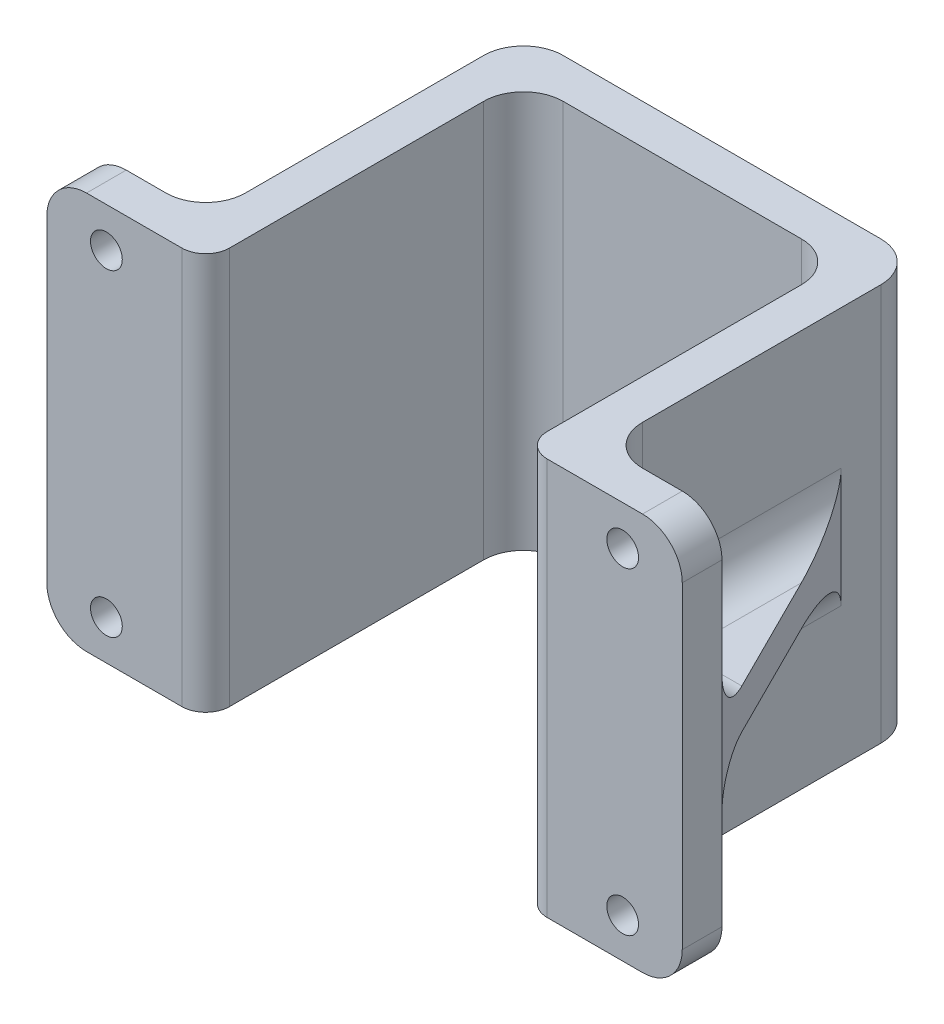
SolidWorks part; units mm, degrees
ref_plane "Front Plane" through (0, 0, 0) normal (0, 0, 1) x (1, 0, 0)
ref_plane "Top Plane" through (0, 0, 0) normal (0, 1, 0) x (1, 0, 0)
ref_plane "Right Plane" through (0, 0, 0) normal (1, 0, 0) x (0, 0, -1)
sketch "Sketch1" plane through (0, 0, 0) normal (0, 1, 0) x (1, 0, 0)
  line L0 (-40, 0) -> (-20, 0)
  line L1 (-20, 0) -> (-20, 40)
  line L2 (-20, 40) -> (20, 40)
  line L3 (20, 40) -> (20, 0)
  line L4 (20, 0) -> (40, 0)
  line L5 (40, 0) -> (40, 5)
  line L6 (40, 5) -> (25, 5)
  line L7 (25, 5) -> (25, 45)
  line L8 (25, 45) -> (-25, 45)
  line L9 (-25, 45) -> (-25, 5)
  line L10 (-25, 5) -> (-40, 5)
  line L11 (-40, 5) -> (-40, 0)
  line L12 (-20, 0) -> (20, 0) construction
  line L13 (0, 0) -> (0, 40) construction
  dimension "D1" = 40
  dimension "D2" = 40
  dimension "D3" = 5
  dimension "D4" = 5
  dimension "D5" = 5
  dimension "D6" = 5
  dimension "D7" = 15
  dimension "D8" = 15
extrude "Boss-Extrude1" add sketch "Sketch1" along normal mid plane 50
fillet "Fillet1" radius 5 6 edges at (-20, 0, -40) (20, 0, -40) (25, 0, -5) (-25, 0, -5) (25, 0, -45) (-25, 0, -45)
sketch "Sketch2" plane through (0, 0, 0) normal (0, 0, 1) x (1, 0, 0)
  line L1 (-32.5, 20) -> (32.5, 20) construction
  line L2 (-32.5, 20) -> (-32.5, -20) construction
  line L3 (-32.5, -20) -> (32.5, -20) construction
  line L4 (32.5, 20) -> (32.5, -20) construction
  line L5 (-32.5, 20) -> (32.5, -20) construction
  line L6 (-32.5, -20) -> (32.5, 20) construction
  circle A0 centre (-32.5, 20) radius 2
  circle A1 centre (-32.5, -20) radius 2
  circle A2 centre (32.5, -20) radius 2
  circle A3 centre (32.5, 20) radius 2
  point P0 (0, 0)
  point P7 (-32.5, 20)
  point P8 (-32.5, -20)
  point P9 (32.5, -20)
  point P10 (32.5, 20)
  dimension "D1" = 65
  dimension "D2" = 40
extrude "Cut-Extrude1" cut sketch "Sketch2" against normal blind 5
fillet "Fillet2" radius 5 4 edges at (40, -25, -2.5) (-40, -25, -2.5) (-40, 25, -2.5) (40, 25, -2.5)
sketch "Sketch3" plane through (0, 0, 0) normal (0, 1, 0) x (1, 0, 0)
  line L0 (-40, 5) -> (-25, 35)
  line L1 (-25, 40) -> (-25, 10) construction
  line L2 (-25, 35) -> (-25, 5)
  line L3 (-25, 5) -> (-40, 5)
  dimension "D1" = 30
extrude "Boss-Extrude2" add sketch "Sketch3" along normal mid plane 5
mirror "Mirror5" about plane through (0, 0, 0) normal (1, 0, 0) of "Boss-Extrude2"
fillet "Fillet3" radius 5 12 edges at (-35, -2.5, -5) (-26.4645, -2.5, -6.4645) (-35, 2.5, -5) (-26.4645, 2.5, -6.4645) (-25, -2.5, -22.5) (-25, 2.5, -22.5) (35, -2.5, -5) (26.4645, -2.5, -6.4645) (35, 2.5, -5) (26.4645, 2.5, -6.4645) (25, -2.5, -22.5) (25, 2.5, -22.5)
fillet "Fillet4" radius 3 2 edges at (20, 0, 0) (-20, 0, 0)
